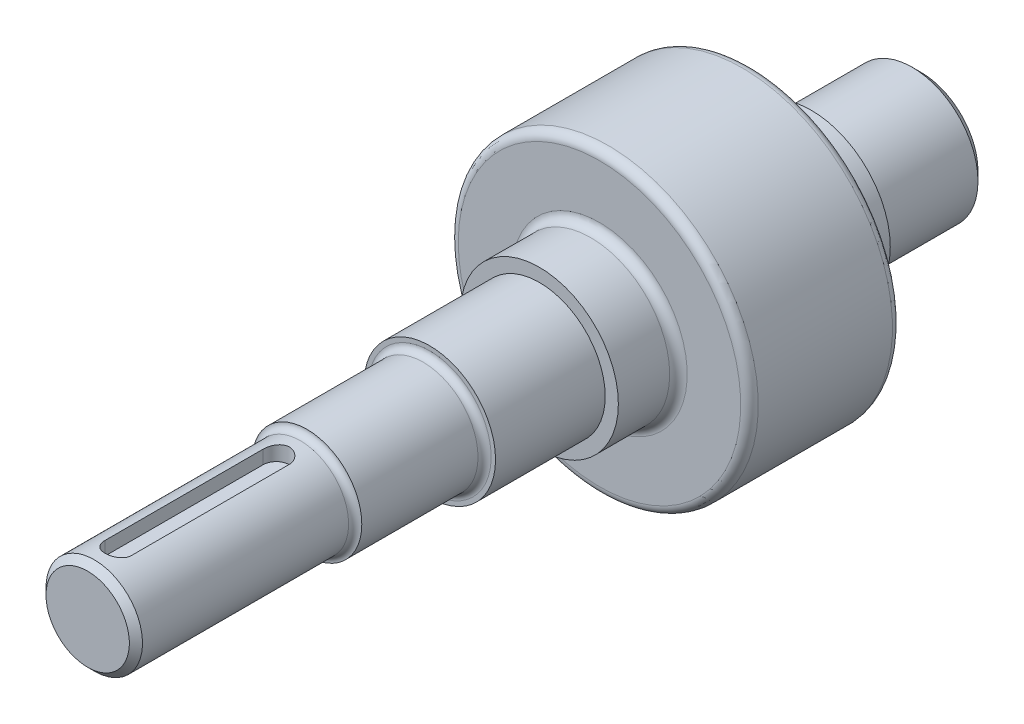
SolidWorks part; units mm, degrees
ref_plane "Front Plane" through (0, 0, 0) normal (0, 0, 1) x (1, 0, 0)
ref_plane "Top Plane" through (0, 0, 0) normal (0, 1, 0) x (1, 0, 0)
ref_plane "Right Plane" through (0, 0, 0) normal (1, 0, 0) x (0, 0, -1)
sketch "Sketch2" plane through (0, 0, 0) normal (1, 0, 0) x (0, 0, -1)
  line L0 (0, 0) -> (0, 11)
  line L1 (0, 11) -> (50, 11)
  line L2 (50, 11) -> (50, 12.5)
  line L3 (50, 12.5) -> (78, 12.5)
  line L4 (78, 12.5) -> (78, 15)
  line L5 (78, 15) -> (103, 15)
  line L6 (103, 15) -> (103, 18)
  line L7 (103, 18) -> (165, 18)
  line L8 (165, 18) -> (165, 15)
  line L9 (165, 15) -> (190, 15)
  line L10 (190, 15) -> (190, 0)
  line L11 (0, 0) -> (190, 0) construction
  line L12 (0, 0) -> (190, 0)
  dimension "D1" = 11
  dimension "D2" = 12.5
  dimension "D3" = 50
  dimension "D4" = 15
  dimension "D5" = 28
  dimension "D6" = 25
  dimension "D7" = 62
  dimension "D8" = 18
  dimension "D9" = 15
  dimension "D10" = 25
revolve "Revolve1" add sketch "Sketch2" angle 360 about L11
ref_plane "Plane1" through (0, 0, -151.3) normal (0, 0, -1) x (-1, 0, 0)
sketch "Sketch3" plane through (0, 0, -151.3) normal (0, 0, -1) x (-1, 0, 0)
  circle A0 centre (0, 0) radius 34.2033
  dimension "D1" = 68.4066
extrude "Boss-Extrude1" add sketch "Sketch3" against normal blind 34.6
fillet "Fillet1" radius 1.5 2 edges at (11, 0, -50) (12.5, 0, -78)
fillet "Fillet2" radius 2 2 edges at (-18, 0, -151.3) (-18, 0, -116.7)
chamfer "Chamfer2" distance 1.5 angle 45 1 edges at (11, 0, 0)
chamfer "Chamfer3" distance 2 angle 45 1 edges at (15, 0, -190)
sketch "Sketch4" plane through (0, 0, -116.7) normal (0, 0, 1) x (1, 0, 0)
  circle A0 centre (0, 0) radius 29.8215
  dimension "D1" = 59.6429
extrude "df1" add sketch "Sketch4" against normal up to surface (34.6 mm away) up to face at (-20, 0, -151.3)
fillet "Fillet3" radius 2 2 edges at (-34.2033, 0, -151.3) (-34.2033, 0, -116.7)
ref_plane "Plane2" through (0, 7.5, 0) normal (0, 1, 0) x (1, 0, 0)
sketch "Sketch5" plane through (0, 7.5, 0) normal (0, 1, 0) x (1, 0, 0)
  line L0 (0, 43) -> (0, 7) construction
  line L1 (3, 43) -> (3, 7)
  line L2 (-3, 43) -> (-3, 7)
  line L3 (-11, 48.5) -> (-11, 1.5) construction
  arc A0 (3, 43) -> (-3, 43) centre (0, 43) ccw
  arc A1 (-3, 7) -> (3, 7) centre (0, 7) ccw
  point P2 (0, 25)
  point P9 (-11, 25)
  dimension "D2" = 36
  dimension "D1" = 6
extrude "Cut-Extrude1" cut sketch "Sketch5" along normal up to next
